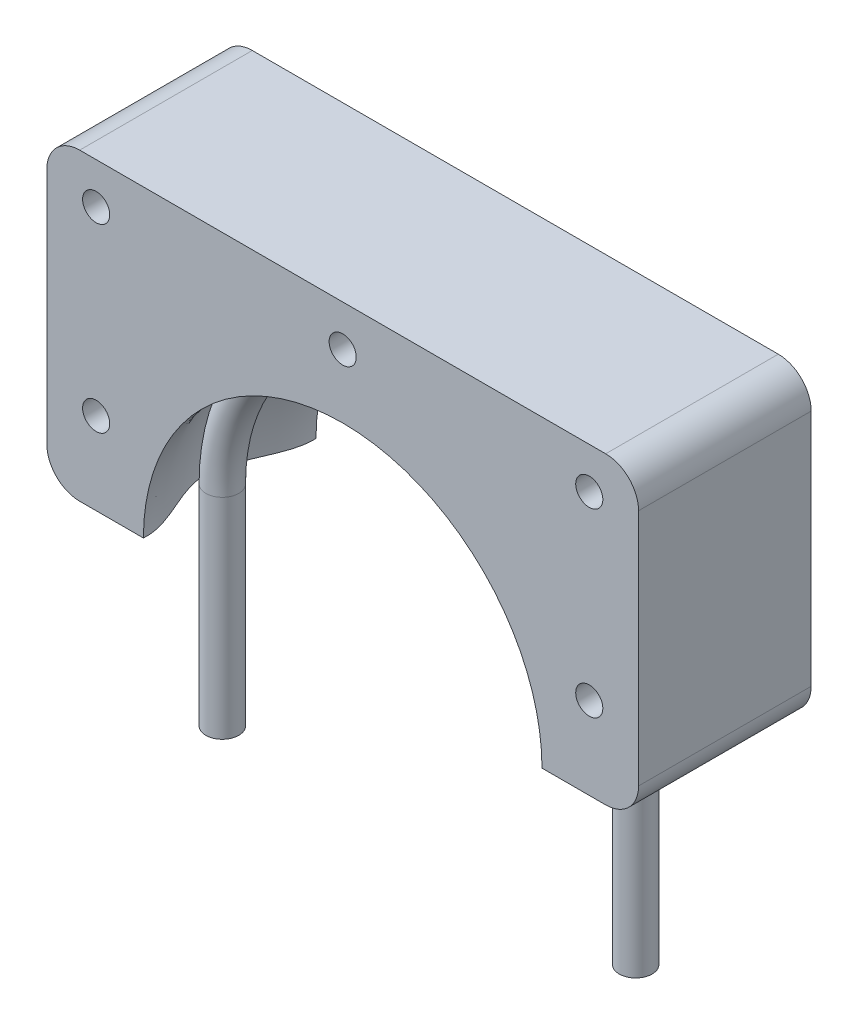
SolidWorks part; units mm, degrees
ref_plane "Front Plane" through (0, 0, 0) normal (0, 0, 1) x (1, 0, 0)
ref_plane "Top Plane" through (0, 0, 0) normal (0, 1, 0) x (1, 0, 0)
ref_plane "Right Plane" through (0, 0, 0) normal (1, 0, 0) x (0, 0, -1)
sketch "Sketch1" plane through (0, 0, 0) normal (0, 0, 1) x (1, 0, 0)
  line L0 (0, 0) -> (-27.25, 0) construction
  line L1 (0, 0) -> (27.25, 0) construction
  line L2 (27.25, 0) -> (-27.25, 0) construction
  line L3 (0, 24.35) -> (0, 27.25) construction
  line L4 (-27.25, 0) -> (-36, 0)
  line L5 (-36, 0) -> (-36, 37)
  line L6 (-36, 37) -> (36, 37)
  line L7 (27.25, 0) -> (36, 0)
  line L8 (36, 0) -> (36, 37)
  line L9 (0, 0) -> (0, 32) construction
  line L10 (0, 32) -> (30, 32) construction
  circle A0 centre (0, 0) radius 24.35 construction
  circle A1 centre (0, 0) radius 27.25
  circle A2 centre (30, 32) radius 1.65
  circle A3 centre (0, 32) radius 1.65
  circle A4 centre (-30, 32) radius 1.65
  circle A5 centre (30, 10) radius 1.65
  circle A6 centre (-30, 10) radius 1.65
  dimension "D1" = 48.7
  dimension "D3" = 2.9
  dimension "D8" = 3.3
  dimension "D9" = 3.3
  dimension "D10" = 22
  dimension "D2" = 180
  dimension "D4" = 37
  dimension "D5" = 72
  dimension "D6" = 30
  dimension "D7" = 32
extrude "Boss-Extrude1" add sketch "Sketch1" along normal mid plane 21 contours A1 L7 L8 L6 L5 L4
sketch "Sketch2" plane through (0, 0, 0) normal (1, 0, 0) x (0, 0, -1)
  line L0 (0, 0) -> (-22.3231, 0) construction
  line L1 (10.5, 0) -> (10.5, 27.25) construction
  line L2 (-10.5, 16.83) -> (-6.6767, 16.83)
  line L3 (10.5, 16.83) -> (4.5, 16.83)
  line L4 (4.5, 16.83) -> (-2.1767, 16.83)
  line L5 (-10.5, 0) -> (10.5, 0) construction
  line L6 (-10.5, 0) -> (-10.5, 16.83) construction
  line L7 (-10.5, 16.83) -> (10.5, 16.83) construction
  line L8 (10.5, 0) -> (10.5, 16.83) construction
  line L9 (10.5, 0) -> (10.5, 37) construction
  line L10 (-2.1767, 16.83) -> (-6.6767, 16.83)
  line L11 (-6.6767, 16.83) -> (-6.6767, 16.13) construction
  line L12 (4.5, 16.83) -> (4.5, 16.13) construction
  line L13 (-10.5, 27.25) -> (-10.5, 0) construction
  line L14 (10.5, 14.83) -> (10.5, 16.83)
  line L15 (-10.5, 14.83) -> (-10.5, 16.83)
  spline S0 degree 3 poles (-10.5, 14.83) (-8.4905, 15.6382) (-1.5563, 17.9262) (5.7798, 15.8466) (10.5, 14.83) knots 0 0 0 0 0.306248 1 1 1 1
  dimension "D1" = 16.83
  dimension "D2" = 6
  dimension "D3" = 4.5
  dimension "D4" = 0.7
  dimension "D5" = 0.7
  dimension "D6" = 2
  dimension "D7" = 2
  dimension "D8" = 0.2
revolve "Revolve1" [suppressed] add sketch "Sketch2" angle 67.5 about L0
fillet "Fillet1" radius 4 4 edges at (36, 37, 0) (-36, 0, 0) (-36, 37, 0) (36, 0, 0)
chamfer "Chamfer2" [suppressed] distance 1 angle 45
sketch "Sketch3" plane through (0, 0, 0) normal (1, 0, 0) x (0, 0, -1)
  line L2 (0, 0) -> (7.6872, 0) construction
  circle A1 centre (-0.047, 25.2604) radius 2
  circle A2 centre (-0.047, 25.2604) radius 0.4
  spline S0 degree 3 poles (9.0434, 25.3816) (6.0798, 25.8564) (-0.0311, 28.6626) (-6.1906, 25.8599) (-9.1188, 25.3688) knots 0 0 0 0 0.500307 1 1 1 1
  dimension "D1" = 4
  dimension "D2" = 0.8
revolve "Revolve2" [suppressed] add sketch "Sketch3" angle 67.5 about L2
chamfer "Chaflán1" [suppressed] distance 0.6 angle 45
sketch "Croquis1" plane through (0, 0, 0) normal (1, 0, 0) x (0, 0, -1)
  line L0 (10.5, 27.25) -> (-10.5, 27.25)
  line L1 (10.5, 0) -> (10.5, 27.25) construction
  line L2 (-10.5, 4) -> (-10.5, 33) construction
  line L3 (-10.5, 27.25) -> (-10.5, 0) construction
  line L4 (-10.5, 27.25) -> (-10.5, 24.25)
  line L5 (10.5, 27.25) -> (10.5, 24.25)
  circle A0 centre (0, 25.15) radius 2 construction
  spline S0 degree 3 poles (10.5, 24.25) (7.1392, 23.9956) (0, 30.3044) (-7.1392, 23.9956) (-10.5, 24.25) knots 0 0 0 0 0.5 1 1 1 1
  point P13 (0, 27.15)
  point P15 (0, 27.25)
  dimension "D8" = 4
  dimension "D1" = 0.1
  dimension "D2" = 0.7
  dimension "D3" = 0.7
  dimension "D4" = 3
  dimension "D5" = 3
  dimension "D6" = 3
  dimension "D7" = 3
revolve "Revolución1" add sketch "Croquis1" angle 90 about axis through (0, 0, 10.5) along (0, 0, -1)
sketch "Croquis2" plane through (0, 0, 0) normal (1, 0, 0) x (0, 0, -1)
  circle A0 centre (0, 25.15) radius 2
  circle A1 centre (0, 25.15) radius 0.4
  dimension "D1" = 4
  dimension "D2" = 0.8
revolve "Revolución2" add sketch "Croquis2" angle 90
sketch "Croquis4" plane through (0, 0, -10.5) normal (0, 0, -1) x (-1, 0, 0)
  text T0 "<b>M</b>" font "Century Gothic" height in points 16
extrude "Cortar-Extruir2" cut sketch "Croquis4" against normal blind 1
fillet "Redondeo1" radius 0.2 2 edges at (14.6645, 28.3391, -10) (15.9128, 26.9458, -10)
sketch "Croquis5" [suppressed] plane through (0, 0, -10.5) normal (0, 0, -1) x (-1, 0, 0)
  text T0 "<b>A</b>" font "Century Gothic" height in points 16
extrude "Cortar-Extruir3" [suppressed] cut sketch "Croquis5" against normal blind 1
sketch "Croquis7" [suppressed] plane through (0, 0, -10.5) normal (0, 0, -1) x (-1, 0, 0)
  text T0 "<b>S</b>" font "Century Gothic" height in points 16
extrude "Cortar-Extruir5" [suppressed] cut sketch "Croquis7" against normal blind 1
sketch "Croquis10" plane through (0, 0, 0) normal (0, -1, 0) x (1, 0, 0)
  circle A0 centre (25.15, 0) radius 2 construction
  circle A1 centre (-25.15, 0) radius 2 construction
  circle A2 centre (25.15, 0) radius 2
  circle A3 centre (-25.15, 0) radius 2
  circle A4 centre (-25.15, 0) radius 0.4 construction
  circle A5 centre (25.15, 0) radius 0.4 construction
  circle A6 centre (-25.15, 0) radius 0.4
  circle A7 centre (25.15, 0) radius 0.4
extrude "Saliente-Extruir1" add sketch "Croquis10" along normal blind 25.5
chamfer "Chaflán2" distance 2 angle 45 5 edges at (-28.35, 32, -10.5) (-28.35, 10, -10.5) (1.65, 32, -10.5) (31.65, 10, -10.5) (31.65, 32, -10.5)
